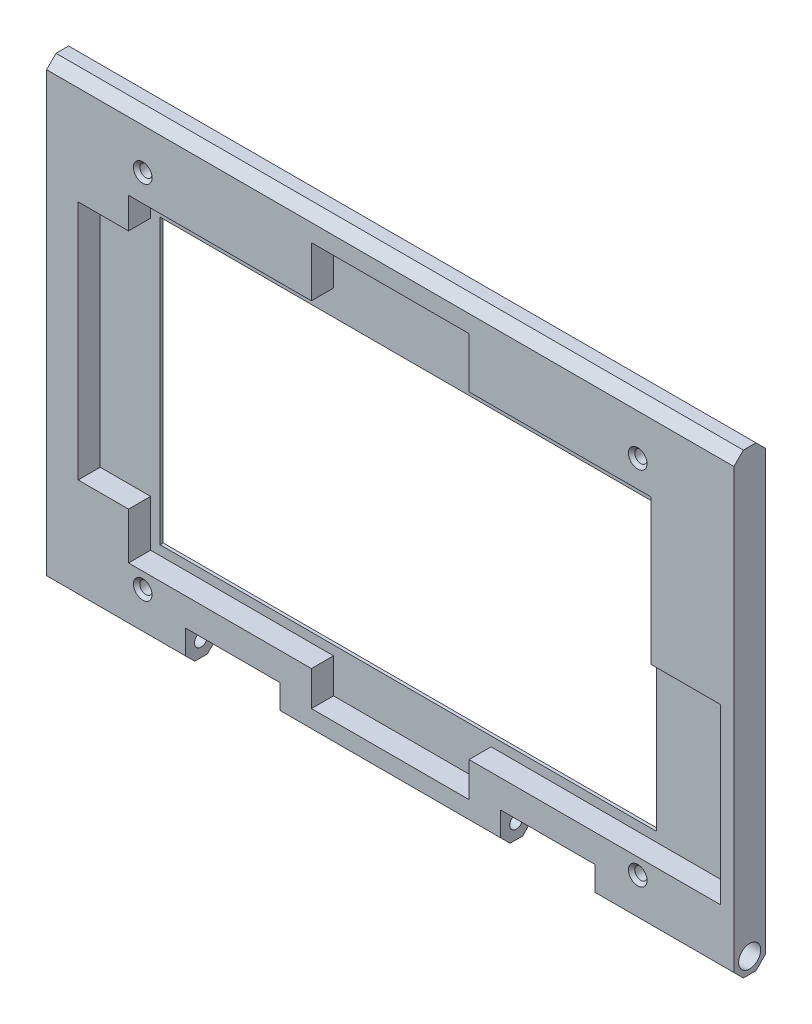
SolidWorks part; units mm, degrees
ref_plane "Alzado" through (0, 0, 0) normal (0, 0, 1) x (1, 0, 0)
ref_plane "Planta" through (0, 0, 0) normal (0, 1, 0) x (1, 0, 0)
ref_plane "Vista lateral" through (0, 0, 0) normal (1, 0, 0) x (0, 0, -1)
sketch "Croquis1" plane through (0, 0, 0) normal (0, 0, 1) x (1, 0, 0)
  line L0 (0, 0) -> (0, 30488.385) construction
  line L1 (0, 0) -> (30488.385, 0) construction
  line L3 (109, -72.5) -> (-109, -72.5)
  line L4 (109, -72.5) -> (109, 72.5)
  line L5 (109, 72.5) -> (-109, 72.5)
  line L6 (-109, -72.5) -> (-109, 72.5)
  line L7 (109, -72.5) -> (-109, 72.5) construction
  line L8 (109, 72.5) -> (-109, -72.5) construction
  line L9 (-83, 43) -> (80.5, 43) construction
  line L10 (-83, 43) -> (-83, -53) construction
  line L11 (-83, -53) -> (80.5, -53) construction
  line L12 (80.5, 43) -> (80.5, -53) construction
  line L13 (-83, 43) -> (80.5, -53) construction
  line L14 (-83, -53) -> (80.5, 43) construction
  line L15 (-80, 40) -> (77.5, 40) construction
  line L16 (-80, 40) -> (-80, -50) construction
  line L17 (-80, -50) -> (77.5, -50) construction
  line L18 (77.5, 40) -> (77.5, -50) construction
  line L19 (-80, 40) -> (77.5, -50) construction
  line L20 (-80, -50) -> (77.5, 40) construction
  circle A0 centre (-78.5, 56.5) radius 1.6 construction
  circle A1 centre (-78.5, -58) radius 1.6 construction
  circle A2 centre (78.5, -58) radius 1.6 construction
  circle A3 centre (78.5, 56.5) radius 1.6 construction
  point P7 (-1.25, -5)
  point P14 (0, 0)
  point P28 (-1.25, -5)
  dimension "D1" = 3.2
  dimension "D2" = 157
  dimension "D3" = 58
  dimension "D4" = 83
  dimension "D5" = 43
  dimension "D6" = 145
  dimension "D7" = 218
  dimension "D8" = 3
  dimension "D9" = 80.5
  dimension "D10" = 53
  dimension "D11" = 3
  dimension "D12" = 3
  dimension "D13" = 3
  dimension "D14" = 56.5
extrude "Saliente-Extruir1" add sketch "Croquis1" along normal blind 10
sketch "Croquis2" plane through (0, 0, 10) normal (0, 0, 1) x (1, 0, 0)
  line L0 (-83, 43) -> (-83, 48)
  line L1 (-83, 43) -> (80.5, 43) construction
  line L2 (-83, 43) -> (-83, -53)
  line L3 (-83, -53) -> (80.5, -53)
  line L4 (80.5, 43) -> (80.5, -53) construction
  line L5 (-83, 43) -> (80.5, -53) construction
  line L6 (-83, -53) -> (80.5, 43) construction
  line L7 (-83, 48) -> (82.7, 48)
  line L8 (82.7, 48) -> (82.7, -53)
  line L9 (82.7, -53) -> (80.5, -53)
  point P4 (-1.25, -5)
  dimension "D1" = 5
  dimension "D2" = 2.2
extrude "Cortar-Extruir1" cut sketch "Croquis2" against normal blind 7
sketch "Croquis3" plane through (0, 0, 3) normal (0, 0, 1) x (1, 0, 0)
  line L1 (-80, 40) -> (77.5, 40)
  line L2 (-80, 40) -> (-80, -50)
  line L3 (-80, -50) -> (77.5, -50)
  line L4 (77.5, 40) -> (77.5, -50)
  line L5 (-80, 40) -> (77.5, -50) construction
  line L6 (-80, -50) -> (77.5, 40) construction
  point P4 (-1.25, -5)
extrude "Cortar-Extruir2" cut sketch "Croquis3" against normal through all
chamfer "Chaflán1" distance 2 angle 45 4 edges at (-80, -5, 0) (-1.25, -50, 0) (77.5, -5, 0) (-1.25, 40, 0)
sketch "Croquis4" plane through (0, 0, 0) normal (0, 0, -1) x (-1, 0, 0)
  circle A0 centre (-78.5, 56.5) radius 1.95
  circle A1 centre (78.5, 56.5) radius 1.95
  circle A2 centre (78.5, -58) radius 1.95
  circle A3 centre (-78.5, -58) radius 1.95
  dimension "D1" = 3.9
extrude "Cortar-Extruir3" cut sketch "Croquis4" against normal through all from offset 2 offset against normal yes
sketch "Croquis5" plane through (0, 0, 10) normal (0, 0, 1) x (1, 0, 0)
  line L0 (0, 0) -> (50000, 0) construction
  line L1 (82.7, -53) -> (104.7, -53)
  line L2 (82.7, -53) -> (82.7, 2)
  line L3 (82.7, 2) -> (104.7, 2)
  line L4 (104.7, -53) -> (104.7, 2)
  line L5 (82.7, -53) -> (104.7, 2) construction
  line L6 (82.7, 2) -> (104.7, -53) construction
  line L7 (27.8965, 0) -> (-49972.1035, 0) construction
  line L8 (0, 0) -> (0, 50000) construction
  line L9 (-83, 48) -> (-83, -53) construction
  line L10 (-99, 38.2043) -> (-83, 38.2043)
  line L11 (-99, 38.2043) -> (-99, -38.2043)
  line L12 (-99, -38.2043) -> (-83, -38.2043)
  line L13 (-83, 38.2043) -> (-83, -38.2043)
  line L14 (-99, 38.2043) -> (-83, -38.2043) construction
  line L15 (-99, -38.2043) -> (-83, 38.2043) construction
  line L17 (-25, 64) -> (25, 64)
  line L18 (-25, 64) -> (-25, 48)
  line L19 (-25, 48) -> (25, 48)
  line L20 (25, 64) -> (25, 48)
  line L21 (-25, 64) -> (25, 48) construction
  line L22 (-25, 48) -> (25, 64) construction
  line L23 (-25, -48) -> (25, -64) construction
  line L24 (-25, -64) -> (25, -48) construction
  line L25 (25, -64) -> (25, -48)
  line L26 (-25, -48) -> (25, -48)
  line L27 (-25, -64) -> (-25, -48)
  line L28 (-25, -64) -> (25, -64)
  line L29 (82.7, 48) -> (-83, 48) construction
  point P4 (93.7, -25.5)
  point P13 (-91, 0)
  point P20 (0, 56)
  point P31 (0, -56)
  dimension "D1" = 22
  dimension "D2" = 55
  dimension "D3" = 16
  dimension "D4" = 50
  dimension "D5" = 16
extrude "Cortar-Extruir4" cut sketch "Croquis5" against normal up to vertex (7 mm away) up to point (77.5, -50, 3)
sketch "Croquis8" plane through (-109, 0, 0) normal (-1, 0, 0) x (0, 0, 1)
  line L0 (5, 72.5) -> (5, -49927.5) construction
  line L1 (10, 72.5) -> (0, 72.5) construction
  line L2 (10, 72.5) -> (0, 72.5) construction
  line L3 (10, -72.5) -> (0, -72.5) construction
  circle A0 centre (5, 67.5) radius 2.1 construction
  circle A1 centre (5, -67.5) radius 2.1
  point P4 (5, 72.5)
  dimension "D1" = 4.2
  dimension "D2" = 5
  dimension "D3" = 5
extrude "Cortar-Extruir6" cut sketch "Croquis8" against normal through all
sketch "Croquis9" plane through (-109, 0, 0) normal (-1, 0, 0) x (0, 0, 1)
  circle A0 centre (5, 67.5) radius 3.5 construction
  circle A1 centre (5, -67.5) radius 3.5
  dimension "D1" = 7
extrude "Cortar-Extruir7" cut sketch "Croquis9" against normal blind 6
mirror "Simetría1" about plane through (0, 0, 0) normal (1, 0, 0) of "Cortar-Extruir7"
chamfer "Chaflán2" distance 3 angle 45 4 edges at (0, 72.5, 10) (0, 72.5, 0) (0, -72.5, 10) (0, -72.5, 0)
sketch "Croquis10" plane through (0, 0, 0) normal (0, 0, -1) x (-1, 0, 0)
  line L0 (0, 0) -> (0, 50000) construction
  line L1 (0, 0) -> (-50000, 0) construction
  line L3 (-65, -72.5) -> (-35, -72.5)
  line L4 (-65, -72.5) -> (-65, -61.8397)
  line L5 (-65, -61.8397) -> (-35, -61.8397)
  line L6 (-35, -72.5) -> (-35, -61.8397)
  line L7 (-65, -72.5) -> (-35, -61.8397) construction
  line L8 (-65, -61.8397) -> (-35, -72.5) construction
  line L10 (35, -72.5) -> (65, -72.5)
  line L11 (35, -72.5) -> (35, -61.8397)
  line L12 (35, -61.8397) -> (65, -61.8397)
  line L13 (65, -72.5) -> (65, -61.8397)
  line L14 (35, -72.5) -> (65, -61.8397) construction
  line L15 (35, -61.8397) -> (65, -72.5) construction
  line L16 (109, -72.5) -> (-109, -72.5) construction
  point P9 (-50, -67.1699)
  point P20 (50, -67.1699)
  dimension "D1" = 10.6603
  dimension "D2" = 30
  dimension "D3" = 50
  dimension "D5" = 50
  dimension "D4" = 2
extrude "Cortar-Extruir8" cut sketch "Croquis10" against normal through all
sketch "Croquis11" plane through (-109, 0, 0) normal (-1, 0, 0) x (0, 0, 1)
  line L0 (7, 72.5) -> (50007, 72.5) construction
  line L1 (-14.1797, 62.5) -> (49985.8203, 62.5) construction
  line L4 (0, 62.5) -> (0, 72.5)
  line L5 (0, 69.5) -> (0, -69.5) construction
  line L6 (0, 72.5) -> (10, 72.5)
  line L7 (10, 72.5) -> (10, 62.5)
  line L8 (10, 69.5) -> (10, -69.5) construction
  line L9 (10, 62.5) -> (26.6642, 62.5)
  line L10 (26.6642, 62.5) -> (26.6642, 52.5)
  line L11 (26.6642, 52.5) -> (10, 52.5)
  line L12 (10, 52.5) -> (0, 62.5)
  dimension "D1" = 45
  dimension "D2" = 10
extrude "Cortar-Extruir9" [suppressed] cut sketch "Croquis11" against normal blind 5 from offset 7 offset against normal yes
mirror "Simetría2" [suppressed] about plane through (0, 0, 0) normal (1, 0, 0)
chamfer "Chaflán3" distance 1 angle 45 4 edges at (76.55, -58, 10) (76.55, 56.5, 10) (-80.45, 56.5, 10) (-80.45, -58, 10)
